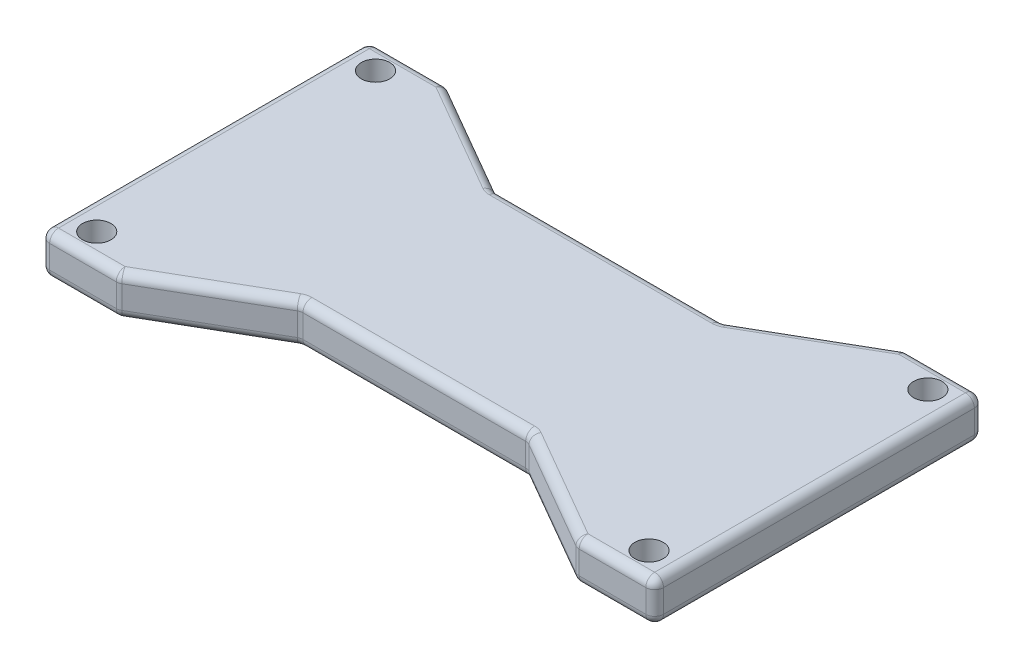
SolidWorks part; units mm, degrees
ref_plane "Front Plane" through (0, 0, 0) normal (0, 0, 1) x (1, 0, 0)
ref_plane "Top Plane" through (0, 0, 0) normal (0, 1, 0) x (1, 0, 0)
ref_plane "Right Plane" through (0, 0, 0) normal (1, 0, 0) x (0, 0, -1)
sketch "Sketch1" plane through (0, 0, 0) normal (0, 1, 0) x (1, 0, 0)
  line L1 (-28.575, 12.7) -> (28.575, 12.7)
  line L2 (-28.575, 12.7) -> (-28.575, -12.7)
  line L3 (-28.575, -12.7) -> (28.575, -12.7)
  line L4 (28.575, 12.7) -> (28.575, -12.7)
  line L5 (-28.575, 12.7) -> (28.575, -12.7) construction
  line L6 (-28.575, -12.7) -> (28.575, 12.7) construction
  point P0 (0, 0)
  dimension "D1" = 25.4
  dimension "D2" = 57.15
sketch "Sketch3" plane through (0, 0, 0) normal (0, 1, 0) x (1, 0, 0)
  line L12 (44.5317, -23.495) -> (53.467, -23.495)
  line L14 (44.5317, 23.495) -> (53.467, 23.495)
  line L17 (53.467, 23.495) -> (53.467, -23.495)
  line L20 (-25.4, -23.495) -> (-34.3353, -23.495)
  line L21 (-25.4, 23.495) -> (-34.3353, 23.495)
  line L24 (-34.3353, -23.495) -> (-34.3353, 23.495)
  line L26 (-25.4, -13.97) -> (44.5317, -13.97)
  line L27 (-25.4, -13.97) -> (-25.4, -23.495)
  line L29 (44.5317, -13.97) -> (44.5317, -23.495)
  line L30 (-25.4, 13.97) -> (44.5317, 13.97)
  line L31 (-25.4, 23.495) -> (-25.4, 13.97)
  line L33 (44.5317, 13.97) -> (44.5317, 23.495)
  circle A17 centre (49.1037, 19.939) radius 2.032
  circle A18 centre (49.1037, -19.939) radius 2.032
  circle A19 centre (-29.8903, -19.939) radius 2.032
  circle A24 centre (-29.8903, 19.939) radius 2.032
  dimension "D1" = 34.3353
  dimension "D2" = 4.445
  dimension "D3" = 4.064
  dimension "D6" = 78.994
  dimension "D9" = 44.5317
  dimension "D8" = 19.939
  dimension "D4" = 3.556
  dimension "D5" = 53.467
  dimension "D7" = 23.495
  dimension "D10" = 13.97
  dimension "D14" = 19.939
extrude "Boss-Extrude1" add sketch "Sketch3" along normal blind 5.842
fillet "Fillet1" radius 1.27 8 edges at (-34.3353, 2.921, -23.495) (53.467, 2.921, -23.495) (53.467, 0, 0) (53.467, 5.842, 0) (53.467, 2.921, 23.495) (-34.3353, 0, 0) (-34.3353, 5.842, 0) (-34.3353, 2.921, 23.495)
chamfer "Chamfer1" distance 10.795 angle 60 4 edges at (-25.4, 2.921, -13.97) (44.5317, 2.921, -13.97) (44.5317, 2.921, 13.97) (-25.4, 2.921, 13.97)
fillet "Fillet2" radius 1.27 36 edges at (53.095, 5.47, 23.123) (53.095, 0.372, 23.123) (-33.9634, 0.372, 23.123) (-33.9634, 5.47, 23.123) (-23.2003, 2.921, 23.495) (47.2645, 5.842, 23.495) (42.332, 2.921, 23.495) (47.2645, 0, 23.495) (34.0831, 5.842, 18.7325) (34.0831, 0, 18.7325) (25.8342, 2.921, 13.97) (9.5658, 0, 13.97) (9.5658, 5.842, 13.97) (-6.7025, 2.921, 13.97) (-14.9514, 5.842, 18.7325) (-14.9514, 0, 18.7325) (-28.1328, 5.842, 23.495) (-28.1328, 0, 23.495) (-33.9634, 5.47, -23.123) (-33.9634, 0.372, -23.123) (53.095, 0.372, -23.123) (53.095, 5.47, -23.123) (-6.7025, 2.921, -13.97) (-14.9514, 5.842, -18.7325) (-14.9514, 0, -18.7325) (-23.2003, 2.921, -23.495) (-28.1328, 5.842, -23.495) (-28.1328, 0, -23.495) (25.8342, 2.921, -13.97) (9.5658, 0, -13.97) (9.5658, 5.842, -13.97) (34.0831, 5.842, -18.7325) (34.0831, 0, -18.7325) (47.2645, 5.842, -23.495) (47.2645, 0, -23.495) (42.332, 2.921, -23.495)
